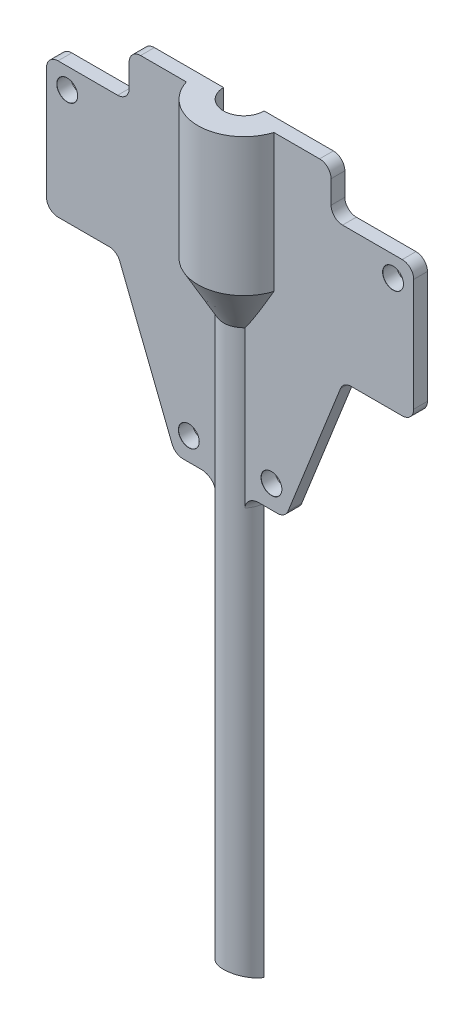
SolidWorks part; units mm, degrees
ref_plane "Front Plane" through (0, 0, 0) normal (0, 0, 1) x (1, 0, 0)
ref_plane "Top Plane" through (0, 0, 0) normal (0, 1, 0) x (1, 0, 0)
ref_plane "Right Plane" through (0, 0, 0) normal (1, 0, 0) x (0, 0, -1)
sketch "Sketch1" plane through (0, 0, 0) normal (0, 0, 1) x (1, 0, 0)
  line L0 (-22, 0) -> (22, 0)
  line L1 (-22, 0) -> (-22, -10)
  line L2 (-22, -10) -> (-40, -10)
  line L3 (-40, -10) -> (-40, -39.5)
  line L4 (-40, -39.5) -> (-24.673, -39.5)
  line L6 (-12, -71.5) -> (12, -71.5)
  line L7 (0, -71.5) -> (0, 0) construction
  line L9 (40, -39.5) -> (24.673, -39.5)
  line L10 (40, -10) -> (40, -39.5)
  line L11 (22, -10) -> (40, -10)
  line L12 (22, 0) -> (22, -10)
  line L13 (-24.673, -39.5) -> (-12, -71.5)
  line L14 (24.673, -39.5) -> (12, -71.5)
  line L15 (-33.3856, -17.5) -> (-24.673, -39.5) construction
  line L16 (33.3856, -17.5) -> (24.673, -39.5) construction
  dimension "D1" = 22
  dimension "D2" = 10
  dimension "D3" = 18
  dimension "D4" = 29.5
  dimension "D5" = 10
  dimension "D6" = 28
  dimension "D7" = 71.5
  dimension "D8" = 17.5
extrude "Boss-Extrude1" add sketch "Sketch1" along normal blind 3
sketch "Sketch2" plane through (0, 0, 0) normal (0, 0, 1) x (1, 0, 0)
  line L0 (-4.425, -165) -> (-4.425, -40)
  line L1 (-4.425, -40) -> (-10, -30)
  line L2 (-10, -30) -> (-10, 0)
  line L3 (-10, 0) -> (0, 0)
  line L4 (0, 0) -> (0, -165)
  line L5 (0, -165) -> (-4.425, -165)
  line L6 (-1.7, -165) -> (-1.7, -34)
  line L7 (-4.425, -34) -> (-1.7, -34)
  line L8 (-4.425, -34) -> (-4.425, 0)
  dimension "D1" = 30
  dimension "D2" = 10
  dimension "D3" = 1.7
  dimension "D4" = 10
  dimension "D5" = 4.425
  dimension "D6" = 125
  dimension "D7" = 131
revolve "Revolve1" add sketch "Sketch2" angle 180 about L4 region at (-3.0625, -118.25, 0) region at (-5.699, -29.6937, 0) reverse direction yes
revolve "Cut-Revolve1" cut sketch "Sketch2<3>" angle 360 about L4 region at (-0.85, -118.25, 0) region at (-1.807, -27.6399, 0)
sketch "Sketch2<3>" plane through (0, 0, 0) normal (0, 0, 1) x (1, 0, 0) same geometry as "Sketch2"
hole_wizard "M4 Clearance Hole1" positions "Sketch4" profile "Sketch5" hole size "M4" standard "ANSI Metric" end condition through all
sketch "Sketch4" plane through (0, 0, 3) normal (0, 0, 1) x (1, 0, 0)
  line L2 (-12, -71.5) -> (-3.2528, -71.5) construction
  line L3 (0, 0) -> (0, -71.5) construction
  line L4 (0, 0) -> (0, -165) construction
  line L6 (3.2528, -71.5) -> (12, -71.5) construction
  line L7 (-22, -10) -> (-40, -10) construction
  line L8 (-40, -10) -> (-40, -39.5) construction
  point P0 (-35.5, -14.5)
  point P2 (-9, -66.5)
  point P26 (9, -66.5)
  point P27 (35.5, -14.5)
  dimension "D1" = 4.5
  dimension "D2" = 4.5
  dimension "D3" = 5
  dimension "D4" = 9
sketch "Sketch5" plane through (-35.5, -14.5, 3) normal (1, 0, 0) x (0, -1, 0)
  line L0 (0, 0) -> (0, 3)
  line L1 (0, 3) -> (2.25, 3)
  line L2 (2.25, 3) -> (2.25, 0.025)
  line L3 (2.25, 0.025) -> (2.275, 0)
  line L5 (2.275, 0) -> (0, 0)
  line L6 (-2.25, 0.025) -> (-2.275, 0) construction
  line L11 (0, -6.35) -> (0, 107.95) construction
  dimension "Thru Hole Dia." = 4.5
  dimension "Thru Hole Depth" = 3
  dimension "Near C'Sink Dia." = 4.55
  dimension "Near C'Sink Angle" = 90
sketch "Sketch7" plane through (0, 0, 0) normal (0, 0, -1) x (-1, 0, 0)
  line L0 (-40, -10) -> (-40, -39.5) construction
  line L1 (-24.673, -39.5) -> (-12, -71.5) construction
  line L2 (-40, -39.5) -> (-24.673, -39.5) construction
  line L3 (0, -165) -> (4.425, -165) construction
  line L4 (-1.7, -165) -> (-4.425, -165) construction
  line L5 (-1.7, -165) -> (1.7, -165) construction
  line L6 (-4.425, -165) -> (-4.425, -71.5) construction
  line L7 (4.425, -165) -> (4.425, -40) construction
  line L8 (12, -71.5) -> (-12, -71.5) construction
  line L9 (24.673, -39.5) -> (12, -71.5) construction
  line L10 (40, -39.5) -> (24.673, -39.5) construction
  line L11 (40, -10) -> (40, -39.5) construction
  line L12 (22, -10) -> (40, -10) construction
  line L13 (22, 0) -> (22, -10) construction
  line L14 (-22, 0) -> (-22, -10) construction
  line L15 (22, 0) -> (-22, 0) construction
  line L16 (-22, -10) -> (-40, -10) construction
  line L17 (-40, -10) -> (-40, -39.5)
  line L18 (-24.673, -39.5) -> (-12, -71.5)
  line L19 (-40, -39.5) -> (-24.673, -39.5)
  line L20 (0, -165) -> (4.425, -165)
  line L21 (-1.7, -165) -> (-4.425, -165)
  line L22 (-1.7, -165) -> (1.7, -165)
  line L23 (-4.425, -165) -> (-4.425, -71.5)
  line L24 (4.425, -165) -> (4.425, -71.5)
  line L25 (12, -71.5) -> (4.425, -71.5)
  line L26 (24.673, -39.5) -> (12, -71.5)
  line L27 (40, -39.5) -> (24.673, -39.5)
  line L28 (40, -10) -> (40, -39.5)
  line L29 (22, -10) -> (40, -10)
  line L30 (22, 0) -> (22, -10)
  line L31 (-22, 0) -> (-22, -10)
  line L32 (22, 0) -> (-22, 0)
  line L33 (-22, -10) -> (-40, -10)
  line L34 (-4.425, -71.5) -> (-12, -71.5)
  line L35 (4.425, -71.5) -> (-4.425, -71.5) construction
  line L36 (4.425, -71.5) -> (4.425, -40) construction
fillet "Fillet1" radius 4 1 edges at (0, -34, 4.425)
fillet "Fillet2" radius 2.5 14 edges at (-40, -10, 1.5) (-22, -10, 1.5) (-22, 0, 1.5) (40, -10, 1.5) (22, 0, 1.5) (22, -10, 1.5) (40, -39.5, 1.5) (24.673, -39.5, 1.5) (12, -71.5, 1.5) (4.1215, -71.5, 1.6104) (-4.1215, -71.5, 1.6104) (-40, -39.5, 1.5) (-24.673, -39.5, 1.5) (-12, -71.5, 1.5)
sketch "Sketch9" plane through (0, 0, 0) normal (1, 0, 0) x (0, 0, -1)
  line L0 (-4.425, -162) -> (4.425, -165)
  line L1 (-4.425, -40) -> (-4.425, -165) construction
  line L2 (4.425, -165) -> (-4.425, -165)
  line L3 (-4.425, -165) -> (-4.425, -162)
  dimension "D1" = 8.85
  dimension "D2" = 3
extrude "Cut-Extrude2" cut sketch "Sketch9" against normal mid plane 10
